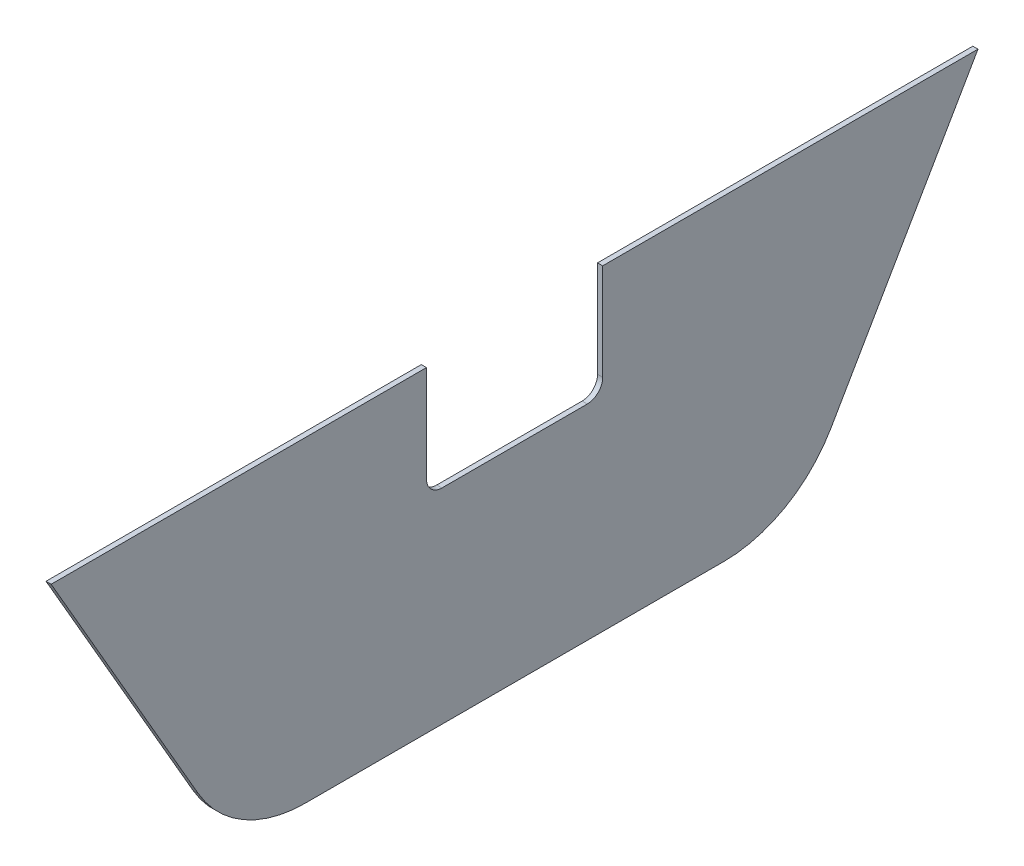
SolidWorks part; units mm, degrees
ref_plane "Front Plane" through (0, 0, 0) normal (0, 0, 1) x (1, 0, 0)
ref_plane "Top Plane" through (0, 0, 0) normal (0, 1, 0) x (1, 0, 0)
ref_plane "Right Plane" through (0, 0, 0) normal (1, 0, 0) x (0, 0, -1)
sketch "Sketch3" plane through (0, 0, 0) normal (1, 0, 0) x (0, 0, -1)
  line L0 (-58.8246, -414.8065) -> (-1.6669, -513.8065)
  line L1 (39.9023, -537.8065) -> (202.4485, -537.8065)
  line L3 (244.0177, -513.8065) -> (301.1754, -414.8065)
  line L6 (155.4004, -414.8065) -> (155.4004, -452.3065)
  line L7 (149.4004, -458.3065) -> (92.9504, -458.3065)
  line L8 (86.9504, -452.3065) -> (86.9504, -414.8065)
  line L9 (98.9504, -426.8065) -> (98.9504, -414.8065) construction
  line L10 (143.4004, -426.8065) -> (143.4004, -414.8065) construction
  line L11 (143.4004, -537.8065) -> (98.9504, -537.8065) construction
  line L12 (-58.8246, -414.8065) -> (86.9504, -414.8065)
  line L13 (155.4004, -414.8065) -> (301.1754, -414.8065)
  arc A0 (202.4485, -537.8065) -> (244.0177, -513.8065) centre (202.4485, -489.8065) ccw
  arc A1 (-1.6669, -513.8065) -> (39.9023, -537.8065) centre (39.9023, -489.8065) ccw
  circle A2 centre (135.1754, -520.8065) radius 2.5 construction
  circle A3 centre (107.1754, -520.8065) radius 2.5 construction
  circle A4 centre (135.1754, -467.8065) radius 2.5 construction
  circle A5 centre (107.1754, -467.8065) radius 2.5 construction
  circle A6 centre (135.1754, -520.8065) radius 2.5
  circle A7 centre (107.1754, -520.8065) radius 2.5
  circle A8 centre (135.1754, -467.8065) radius 2.5
  circle A9 centre (107.1754, -467.8065) radius 2.5
  arc A10 (111.3647, -430.8065) -> (130.9861, -430.8065) centre (121.1754, -442.8065) ccw construction
  arc A11 (155.4004, -452.3065) -> (149.4004, -458.3065) centre (149.4004, -452.3065) cw
  arc A12 (86.9504, -452.3065) -> (92.9504, -458.3065) centre (92.9504, -452.3065) ccw
  point P11 (230.1613, -537.8065)
  dimension "D3" = 48
  dimension "D6" = 6
  dimension "D1" = 60
  dimension "D2" = 60
  dimension "D4" = 12
  dimension "D5" = 12
extrude "Boss-Extrude1" add sketch "Sketch3" along normal blind 2 contours L1 A0 L3 L13 L6 A11 L7 A12 L8 L12 L0 A1
